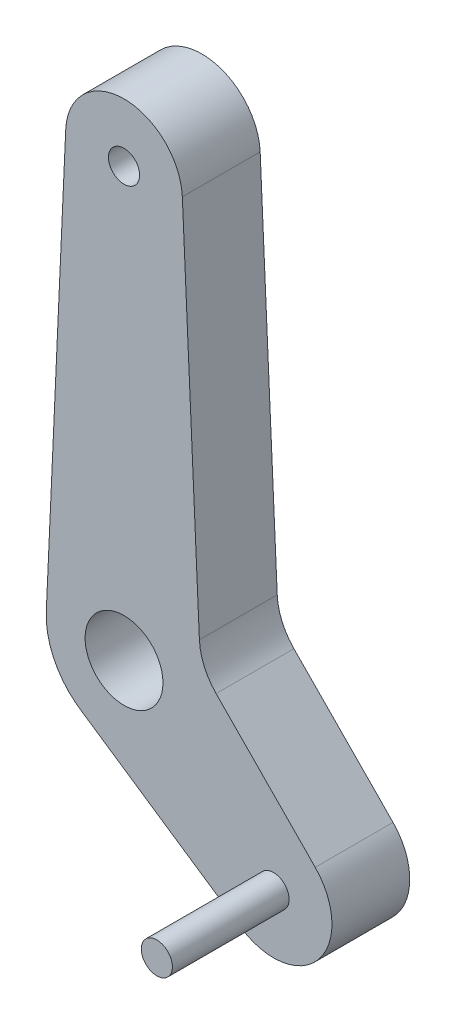
SolidWorks part; units mm, degrees
ref_plane "前视基准面" through (0, 0, 0) normal (0, 0, 1) x (1, 0, 0)
ref_plane "上视基准面" through (0, 0, 0) normal (0, 1, 0) x (1, 0, 0)
ref_plane "右视基准面" through (0, 0, 0) normal (1, 0, 0) x (0, 0, -1)
other "Configuration Table"
sketch "草图1" plane through (0, 0, 0) normal (0, 0, 1) x (1, 0, 0)
  line L0 (-14.9845, 110.6818) -> (-19.9793, 0.9091)
  line L5 (0, 0) -> (38.4309, -31.9854) construction
  line L6 (-10.5592, -16.9854) -> (30.0327, -44.414)
  line L7 (14.9845, 110.6818) -> (19.3705, 14.2904)
  line L8 (49.1314, -21.4734) -> (23.6545, 4.4603)
  arc A6 (-19.9793, 0.9091) -> (-10.5592, -16.9854) centre (0, 0) ccw
  circle A7 centre (0, 0) radius 10
  circle A8 centre (0, 110) radius 4
  arc A9 (14.9845, 110.6818) -> (-14.9845, 110.6818) centre (0, 110) ccw
  arc A10 (30.0327, -44.414) -> (49.1314, -21.4734) centre (38.4309, -31.9854) ccw
  arc A11 (19.3705, 14.2904) -> (23.6545, 4.4603) centre (34.355, 14.9722) ccw
  dimension "D1" = 15
extrude "凸台-拉伸1" add sketch "草图1" along normal blind 20
sketch "草图3" plane through (0, 0, 20) normal (0, 0, 1) x (1, 0, 0)
  circle A0 centre (38.4309, -31.9854) radius 4
  point P3 (0, 0)
extrude "凸台-拉伸2" add sketch "草图3" along normal blind 30
